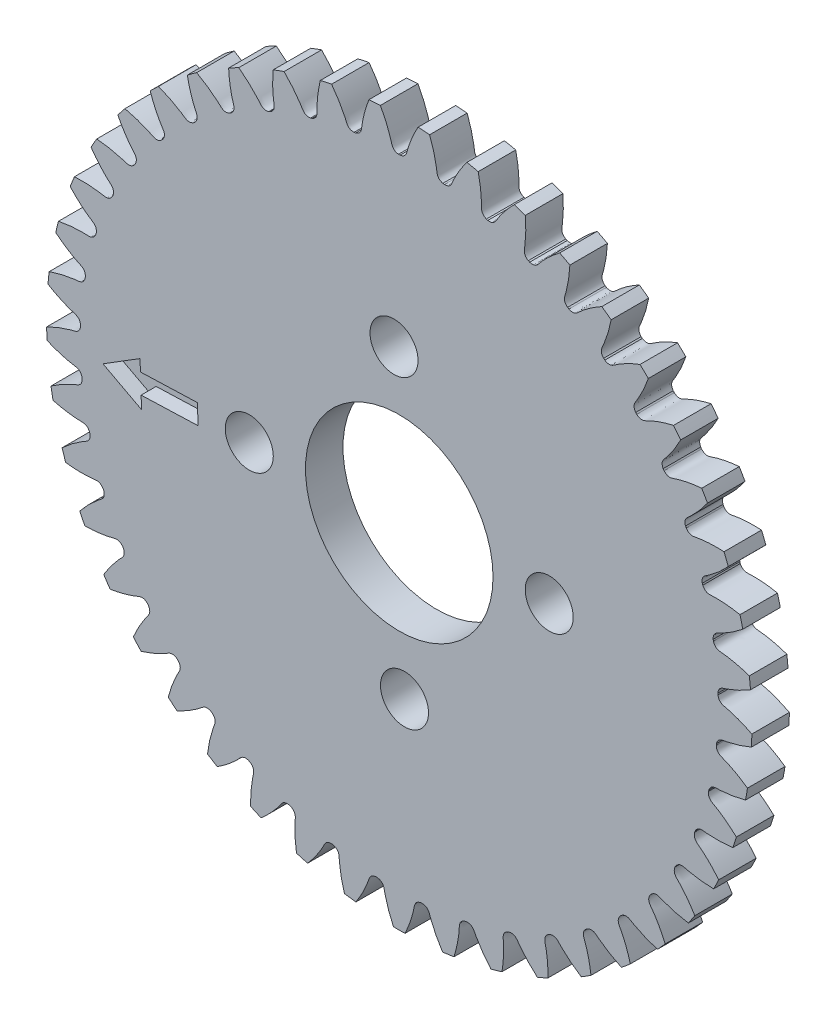
SolidWorks part; units mm, degrees
ref_plane "前视基准面" through (0, 0, 0) normal (0, 0, 1) x (1, 0, 0)
ref_plane "上视基准面" through (0, 0, 0) normal (0, 1, 0) x (1, 0, 0)
ref_plane "右视基准面" through (0, 0, 0) normal (1, 0, 0) x (0, 0, -1)
other "Configuration Table"
sketch "草图1" plane through (0, 0, 0) normal (0, 0, 1) x (1, 0, 0)
  circle A0 centre (0, 0) radius 23.5
extrude "凸台-拉伸1" add sketch "草图1" along normal blind 2.5
ref_axis "基准轴1" through (0, 0, 2.5) along (0, 0, -1)
sketch "草图2" plane through (0, 0, 0) normal (0, 0, 1) x (1, 0, 0)
  line L0 (0, 0) -> (0, 23.5) construction
  circle A0 centre (0, 0) radius 23.5 construction
  arc A1 (0.0519, 21.2499) -> (-0.0519, 21.2499) centre (0, 0) ccw
  arc A2 (3.8286, 26.7057) -> (-3.8286, 26.7057) centre (0, 0) ccw
  spline S0 degree 3 poles (0.0519, 21.2499) (0.4436, 21.3041) (0.4881, 21.5947) (0.5806, 21.9096) (0.6162, 22.0237) (0.6568, 22.145) (0.7027, 22.2735) (0.7541, 22.4089) (0.8114, 22.5512) (0.8748, 22.7) (0.9447, 22.8553) (1.0213, 23.0167) (1.1048, 23.1842) (1.1956, 23.3575) (1.294, 23.5363) (1.4001, 23.7204) (1.5142, 23.9097) (1.6367, 24.1037) (1.7676, 24.3024) (1.9073, 24.5053) (2.0559, 24.7123) (2.2137, 24.923) (2.3809, 25.1372) (2.5577, 25.3546) (2.7442, 25.5749) (2.9408, 25.7977) (3.1474, 26.0228) (3.4406, 26.3296) (3.6704, 26.5559) (3.8286, 26.7057) knots 0 0 0 0 0.112268 0.128789 0.146568 0.165606 0.185901 0.207456 0.230268 0.254339 0.279668 0.306255 0.334101 0.363205 0.393567 0.425188 0.458067 0.492204 0.527599 0.564253 0.602166 0.641336 0.681765 0.723452 0.766398 0.810601 0.856064 0.902784 1 1 1 1
  spline S1 degree 3 poles (-0.0519, 21.2499) (-0.4436, 21.3041) (-0.4881, 21.5947) (-0.5806, 21.9096) (-0.6162, 22.0237) (-0.6568, 22.145) (-0.7027, 22.2735) (-0.7541, 22.4089) (-0.8114, 22.5512) (-0.8748, 22.7) (-0.9447, 22.8553) (-1.0213, 23.0167) (-1.1048, 23.1842) (-1.1956, 23.3575) (-1.294, 23.5363) (-1.4001, 23.7204) (-1.5142, 23.9097) (-1.6367, 24.1037) (-1.7676, 24.3024) (-1.9073, 24.5053) (-2.0559, 24.7123) (-2.2137, 24.923) (-2.3809, 25.1372) (-2.5577, 25.3546) (-2.7442, 25.5749) (-2.9408, 25.7977) (-3.1474, 26.0228) (-3.4406, 26.3296) (-3.6704, 26.5559) (-3.8286, 26.7057) knots 0 0 0 0 0.112268 0.128789 0.146568 0.165606 0.185901 0.207456 0.230268 0.254339 0.279668 0.306255 0.334101 0.363205 0.393567 0.425188 0.458067 0.492204 0.527599 0.564253 0.602166 0.641336 0.681765 0.723452 0.766398 0.810601 0.856064 0.902784 1 1 1 1
extrude "切除-拉伸1" cut sketch "草图2" along normal through all
pattern_circular "阵列(圆周)1" count 45 every 8 about axis through (0, 0, 2.5) along (0, 0, -1) of "切除-拉伸1"
sketch "草图3" plane through (0, 0, 0) normal (0, 0, 1) x (1, 0, 0)
  circle A0 centre (0, 0) radius 22.5 construction
  dimension "Dn" = 45
sketch "草图4" plane through (0, 0, 2.5) normal (0, 0, 1) x (1, 0, 0)
  circle A0 centre (0, 0) radius 6.25
  dimension "D1" = 12.5
extrude "切除-拉伸2" cut sketch "草图4" against normal blind 10
sketch "草图5" plane through (0, 0, 2.5) normal (0, 0, 1) x (1, 0, 0)
  line L0 (0, 0) -> (-23.4857, -0.8201) construction
  circle A0 centre (0, 0) radius 10 construction
  arc A5 (-23.496, -0.4361) -> (-23.4691, -1.204) centre (0, 0) ccw construction
  circle A6 centre (-9.9939, -0.349) radius 1.6
  circle A7 centre (0, 0) radius 10 construction
  circle A8 centre (-0.349, 9.9939) radius 1.6
  circle A9 centre (0, 0) radius 10 construction
  circle A10 centre (9.9939, 0.349) radius 1.6
  circle A11 centre (0, 0) radius 10 construction
  circle A12 centre (0.349, -9.9939) radius 1.6
  point P21 (0, 0)
  dimension "D1" = 20
  dimension "D2" = 3.2
  dimension "D3" = 4
extrude "切除-拉伸3" cut sketch "草图5" against normal blind 10
sketch "草图6" plane through (0, 0, 2.5) normal (0, 0, 1) x (1, 0, 0)
  line L0 (-9.9939, -0.349) -> (-23.4857, -0.8201)
  line L1 (-23.4857, -0.8201) -> (21.2352, 0.7935)
  arc A0 (-23.496, -0.4361) -> (-23.4691, -1.204) centre (0, 0) ccw construction
sketch "草图7" plane through (0, 0, 2.5) normal (0, 0, 1) x (1, 0, 0)
  line L0 (-9.9939, -0.349) -> (-23.4857, -0.8201) construction
  line L1 (-19.7439, -0.6895) -> (-17.2736, 0.8469)
  line L2 (-17.2736, 0.8469) -> (-17.247, 0.0854)
  line L3 (-17.247, 0.0854) -> (-13.4509, 0.2179)
  line L4 (-13.4509, 0.2179) -> (-13.4051, -1.0931)
  line L5 (-13.4051, -1.0931) -> (-17.2012, -1.2257)
  line L6 (-17.2012, -1.2257) -> (-17.1725, -2.0498)
  line L7 (-17.1725, -2.0498) -> (-19.7439, -0.6895)
  arc A0 (-23.496, -0.4361) -> (-23.4691, -1.204) centre (0, 0) ccw construction
extrude "切除-拉伸4" cut sketch "草图7" against normal blind 1 contours L7 L1 L2 L3 L4 L5 L6
